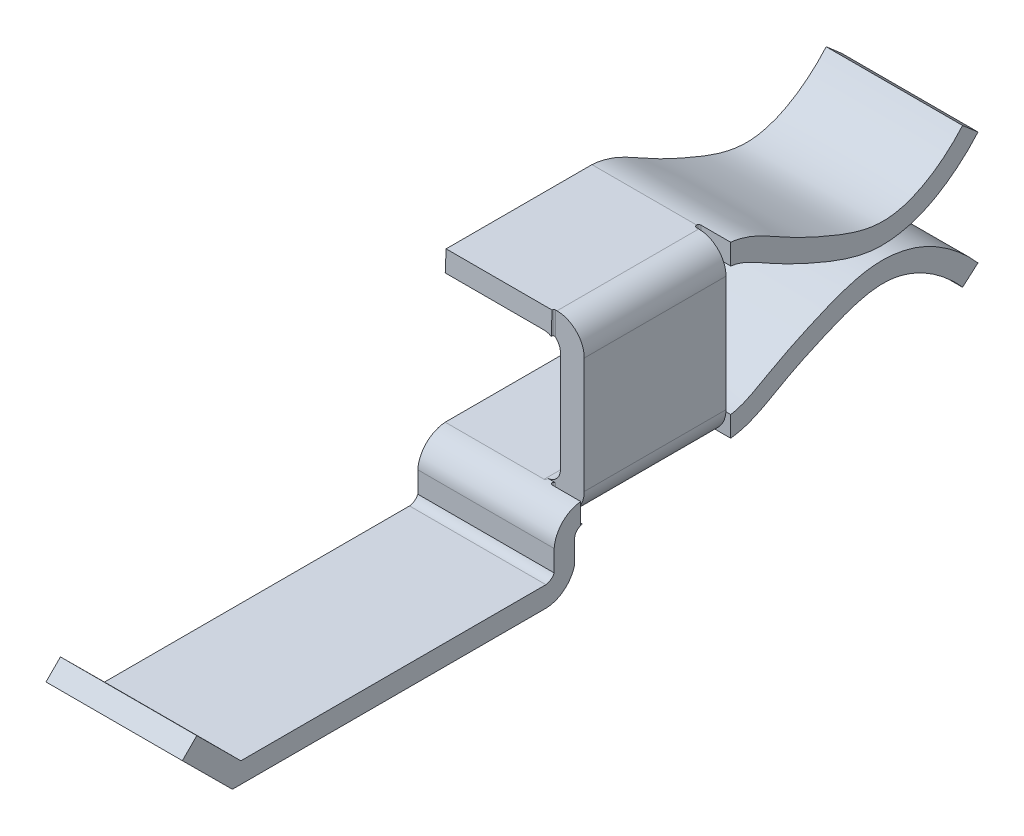
SolidWorks part; units mm, degrees
ref_plane "Спереди" through (0, 0, 0) normal (0, 0, 1) x (1, 0, 0)
ref_plane "Сверху" through (0, 0, 0) normal (0, 1, 0) x (1, 0, 0)
ref_plane "Справа" through (0, 0, 0) normal (1, 0, 0) x (0, 0, -1)
sketch "Эскиз1" plane through (0, 0, 0) normal (1, 0, 0) x (0, 0, -1)
  line L0 (0, 0) -> (2.1388, 0)
  line L1 (-0.1153, -0.1154) -> (-0.1153, -0.4586)
  line L2 (-0.0128, 0.3) -> (2.1286, 0.3)
  line L3 (-0.5254, -0.8017) -> (-5.1337, -0.8017)
  line L4 (-5.1337, -0.8017) -> (-5.8675, -0.0719)
  line L5 (-0.4153, -0.1028) -> (-0.4153, -0.4131)
  line L6 (-0.5367, -0.5017) -> (-5.0099, -0.5017)
  line L7 (-5.0099, -0.5017) -> (-5.656, 0.1408)
  line L8 (-5.656, 0.1408) -> (-5.8675, -0.0719)
  line L9 (5.8002, 0.4164) -> (5.5735, 0.2199)
  line L10 (7.4547, 1.2476) -> (-0.4153, 1.2476) construction
  line L11 (5.8002, 2.0789) -> (5.5735, 2.2753)
  line L12 (-0.0128, 2.1953) -> (2.1286, 2.1953)
  line L13 (0, 2.4953) -> (2.1388, 2.4953)
  line L14 (0, 2.4953) -> (-0.0128, 2.1953)
  arc A0 (0, 0) -> (-0.1153, -0.1154) centre (0.0157, -0.131) ccw
  arc A1 (-0.0128, 0.3) -> (-0.4153, -0.1028) centre (0.0157, -0.131) ccw
  arc A2 (-0.1153, -0.4586) -> (-0.5254, -0.8017) centre (-0.552, -0.3533) cw
  arc A3 (-0.4153, -0.4131) -> (-0.5367, -0.5017) centre (-0.552, -0.3533) cw
  spline S0 degree 3 poles (2.1388, 0) (2.4507, 0.0194) (2.9038, 0.3258) (3.6495, 0.6676) (4.6031, 1.0335) (5.3043, 0.5305) (5.5735, 0.2199) knots 0 0 0 0 0.240586 0.420612 0.660757 1 1 1 1
  spline S1 degree 1 poles (2.1286, 0.3) (5.8002, 0.4164) knots 0 0 1 1 construction
  spline S2 degree 3 poles (5.8002, 0.4164) (5.6825, 0.5522) (5.4234, 0.7947) (4.9274, 1.0923) (4.3183, 1.1936) (3.769, 1.039) (3.3156, 0.8444) (2.8688, 0.6335) (2.4497, 0.3806) (2.2469, 0.3089) (2.1286, 0.3) knots 0.003194 0.003194 0.003194 0.003194 0.127795 0.252396 0.376997 0.501597 0.626198 0.750799 0.875399 1 1 1 1
  spline S3 degree 3 poles (5.8002, 2.0789) (5.6825, 1.9431) (5.4234, 1.7006) (4.9274, 1.403) (4.3183, 1.3016) (3.769, 1.4563) (3.3156, 1.6509) (2.8688, 1.8618) (2.4497, 2.1147) (2.2469, 2.1863) (2.1286, 2.1953) knots 0.003194 0.003194 0.003194 0.003194 0.127795 0.252396 0.376997 0.501597 0.626198 0.750799 0.875399 1 1 1 1
  spline S4 degree 3 poles (2.1388, 2.4953) (2.4507, 2.4759) (2.9038, 2.1694) (3.6495, 1.8277) (4.6031, 1.4618) (5.3043, 1.9648) (5.5735, 2.2753) knots 0 0 0 0 0.240586 0.420612 0.660757 1 1 1 1
  point P9 (-0.1153, -0.8017)
  dimension "D1" = 0.3
  dimension "D2" = 1.2476
extrude "Бобышка-Вытянуть1" add sketch "Эскиз1" against normal blind 2
sketch "Эскиз2" plane through (0, 0.3, 0) normal (0, 1, 0) x (1, 0, 0)
  line L0 (-2, 2.1286) -> (0, 2.1286) construction
  line L1 (0, 0) -> (-0.35, 0)
  line L2 (0, 0) -> (0, 2.1286)
  line L3 (0, 2.1286) -> (-0.35, 2.1286)
  line L4 (-0.35, 0) -> (-0.35, 2.1286)
  dimension "D1" = 0.35
extrude "Бобышка-Вытянуть2" add sketch "Эскиз2" along normal up to next
sketch "Эскиз4" plane through (0, 2.4953, 0) normal (0, 1, 0) x (1, 0, 0)
  line L0 (0.432, 2.1388) -> (-0.432, 2.1388) construction
  line L1 (-2, 2.1388) -> (0, 2.1388) construction
  line L2 (0.432, 2.1046) -> (-0.432, 2.1046)
  line L3 (0.432, 2.1731) -> (-0.432, 2.1731)
  arc A0 (0.432, 2.1046) -> (0.432, 2.1731) centre (0.432, 2.1388) ccw
  arc A1 (-0.432, 2.1731) -> (-0.432, 2.1046) centre (-0.432, 2.1388) ccw
  point P6 (0, 2.1388)
extrude "Вырез-Вытянуть1" cut sketch "Эскиз4" against normal through all
sketch "Эскиз5" plane through (0, 0, 0) normal (0, -1, 0) x (1, 0, 0)
  line L0 (0.4204, 0) -> (-0.4204, 0) construction
  line L1 (-2, 0) -> (0, 0) construction
  line L2 (0.4204, -0.0256) -> (-0.4204, -0.0256)
  line L3 (0.4204, 0.0256) -> (-0.4204, 0.0256)
  arc A0 (0.4204, -0.0256) -> (0.4204, 0.0256) centre (0.4204, 0) ccw
  arc A1 (-0.4204, 0.0256) -> (-0.4204, -0.0256) centre (-0.4204, 0) ccw
  point P5 (0, 0)
extrude "Вырез-Вытянуть2" cut sketch "Эскиз5" against normal blind 2.64
fillet "Скругление3" radius 0.4 2 edges at (0, 2.4953, -1.0651) (0, 0, -1.0651)
fillet "Скругление5" radius 0.2 2 edges
